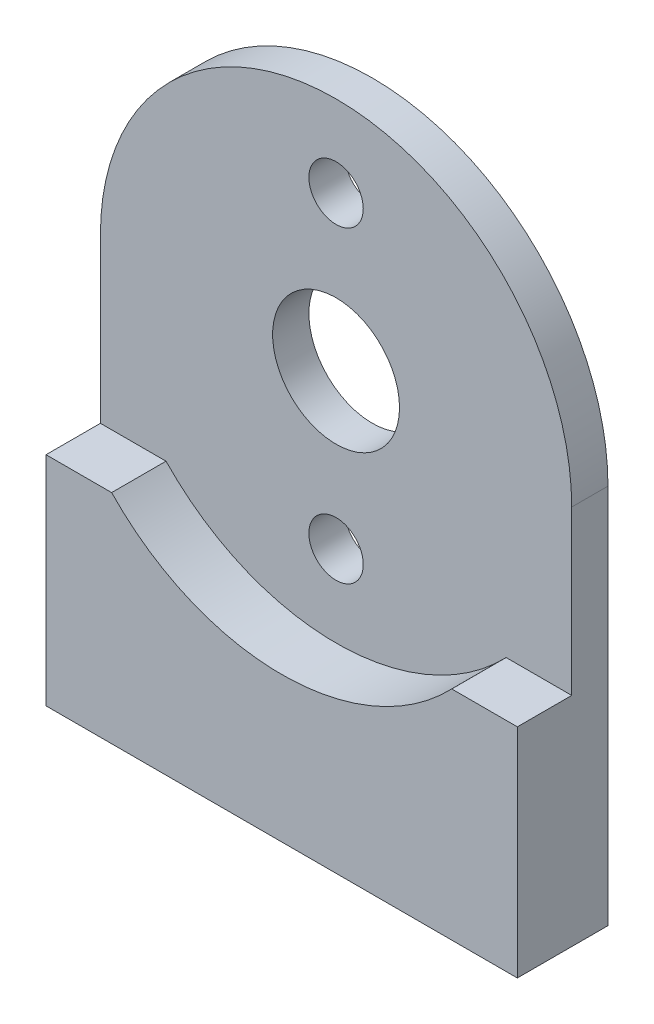
SolidWorks part; units mm, degrees
ref_plane "Front Plane" through (0, 0, 0) normal (0, 0, 1) x (1, 0, 0)
ref_plane "Top Plane" through (0, 0, 0) normal (0, 1, 0) x (1, 0, 0)
ref_plane "Right Plane" through (0, 0, 0) normal (1, 0, 0) x (0, 0, -1)
sketch "Sketch1" plane through (0, 0, 0) normal (0, 0, 1) x (1, 0, 0)
  line L0 (0, 23.5149) -> (0, -21.1386) construction
  line L1 (-28.4158, 0) -> (26.4356, 0) construction
  line L2 (-16.2317, 10.5) -> (18.4954, 10.5) construction
  line L4 (-13, 10.5) -> (-13, -10.5)
  line L5 (-13, -10.5) -> (13, -10.5)
  line L6 (13, 10.5) -> (13, -10.5)
  arc A0 (13, 10.5) -> (-13, 10.5) centre (0, 10.5) ccw
  circle A1 centre (0, 10.5) radius 3.5
  circle A2 centre (0, 10.5) radius 8.5 construction
  circle A5 centre (0, 19) radius 1.5
  circle A6 centre (0, 2) radius 1.5
  point P10 (-13, 0)
  dimension "D1" = 26
  dimension "D3" = 21
  dimension "D4" = 17
  dimension "D5" = 3
  dimension "D7" = 3
  dimension "D8" = 7
  dimension "D2" = 21
  dimension "D6" = 21
extrude "Boss-Extrude1" add sketch "Sketch1" along normal mid plane 2
sketch "Sketch7" plane through (0, 0, 1) normal (0, 0, 1) x (1, 0, 0)
  line L0 (-13, 10.5) -> (-13, -10.5) construction
  line L1 (13, -10.5) -> (-13, -10.5)
  line L2 (13, -10.5) -> (13, 1.5)
  line L3 (13, 1.5) -> (9.3808, 1.5)
  line L4 (-13, -10.5) -> (-13, 1.5)
  line L5 (-9.3808, 1.5) -> (-13, 1.5)
  arc A0 (-9.3808, 1.5) -> (9.3808, 1.5) centre (0, 10.5) ccw
  dimension "D2" = 26
  dimension "D1" = 12
extrude "Boss-Extrude4" add sketch "Sketch7" along normal blind 3
sketch "Sketch8" plane through (0, -10.5, 0) normal (0, -1, 0) x (1, 0, 0)
  line L0 (-13, 1.5) -> (13, 1.5) construction
  line L1 (-13, 4) -> (-13, -1) construction
  line L2 (13, 4) -> (13, -1) construction
  circle A0 centre (-10, 1.5) radius 1.5
  circle A1 centre (10, 1.5) radius 1.5
  dimension "D1" = 3
  dimension "D2" = 3
  dimension "D3" = 3
  dimension "D4" = 3
sketch "Sketch9" plane through (0, -10.5, 0) normal (0, -1, 0) x (1, 0, 0)
  line L0 (-13, 1.5) -> (13, 1.5) construction
  line L1 (-13, 4) -> (-13, -1) construction
  line L2 (13, 4) -> (13, -1) construction
  line L3 (0, 6.9854) -> (0, -3.8204) construction
  circle A0 centre (-5, 1.5) radius 1.5
  circle A1 centre (5, 1.5) radius 1.5
  dimension "D1" = 3
  dimension "D2" = 3
  dimension "D3" = 5
  dimension "D4" = 5
hole_wizard "Ø3.0mm Dowel Hole2" positions "3DSketch3" profile "Sketch17" hole size "Ø3.0" standard "ISO"
sketch3d "3DSketch3"
  point P0 (-10, -10.5, 1.5)
  point P3 (10, -10.5, 1.5)
sketch "Sketch17" plane through (-10, -10.5, 1.5) normal (1, 0, 0) x (0, 0, -1)
  line L0 (0, 0) -> (0, 7.9013)
  line L1 (0, 7.9013) -> (1.5, 7)
  line L2 (1.5, 7) -> (1.5, 0)
  line L5 (1.5, 0) -> (0, 0)
  line L10 (0, 7.9013) -> (-1.5, 7) construction
  line L11 (0, -6.35) -> (0, 107.95) construction
  dimension "Hole Dia." = 3
  dimension "Hole Depth" = 7
  dimension "Drill Angle" = 118
hole_wizard "Ø2.5mm Dowel Hole1" positions "3DSketch4" profile "Sketch18" hole size "Ø2.5" standard "ISO"
sketch3d "3DSketch4"
  point P0 (-5, -10.5, 1.5)
  point P3 (5, -10.5, 1.5)
sketch "Sketch18" plane through (-5, -10.5, 1.5) normal (1, 0, 0) x (0, 0, -1)
  line L0 (0, 0) -> (0, 7.7511)
  line L1 (0, 7.7511) -> (1.25, 7)
  line L2 (1.25, 7) -> (1.25, 0)
  line L5 (1.25, 0) -> (0, 0)
  line L10 (0, 7.7511) -> (-1.25, 7) construction
  line L11 (0, -6.35) -> (0, 107.95) construction
  dimension "Hole Dia." = 2.5
  dimension "Hole Depth" = 7
  dimension "Drill Angle" = 118
thread "Thread1" pitch 0.5 method cut profile "Thread Profile2" start angle 0, offset 0, length 6, pitch 0.5, diameter 2.5
ref_plane "Plane2" through (-3.75, -10.5, 1.5) normal (0, 0, 1) x (1, 0, 0)
sketch "Thread Profile2" plane through (-3.75, -10.5, 1.5) normal (0, 0, 1) x (1, 0, 0)
  line L0 (0, 0) -> (0, 0.5) construction
  line L1 (0, 0) -> (0.2706, 0.1562)
  line L2 (0.2706, 0.1562) -> (0.2706, 0.2187)
  line L3 (0.2706, 0.2187) -> (0, 0.375)
  line L4 (0.2706, 0.1875) -> (0, 0.1875) construction
  line L11 (0, 0) -> (0, 0.375)
  point P2 (0, 0)
  dimension "Pitch" = 0.5
  dimension "Profile_Angle" = 60
  dimension "Profile_Land" = 0.0625
  dimension "Profile_Height" = 0.2706
thread "Thread3" pitch 0.5 method cut profile "Thread Profile4" start angle 0, offset 0, length 6, pitch 0.5, diameter 2.5
ref_plane "Plane4" through (6.25, -10.5, 1.5) normal (0, 0, 1) x (1, 0, 0)
sketch "Thread Profile4" plane through (6.25, -10.5, 1.5) normal (0, 0, 1) x (1, 0, 0)
  line L0 (0, 0) -> (0, 0.5) construction
  line L1 (0, 0) -> (0.2706, 0.1562)
  line L2 (0.2706, 0.1562) -> (0.2706, 0.2187)
  line L3 (0.2706, 0.2187) -> (0, 0.375)
  line L4 (0.2706, 0.1875) -> (0, 0.1875) construction
  line L11 (0, 0) -> (0, 0.375)
  point P2 (0, 0)
  dimension "Pitch" = 0.5
  dimension "Profile_Angle" = 60
  dimension "Profile_Land" = 0.0625
  dimension "Profile_Height" = 0.2706
